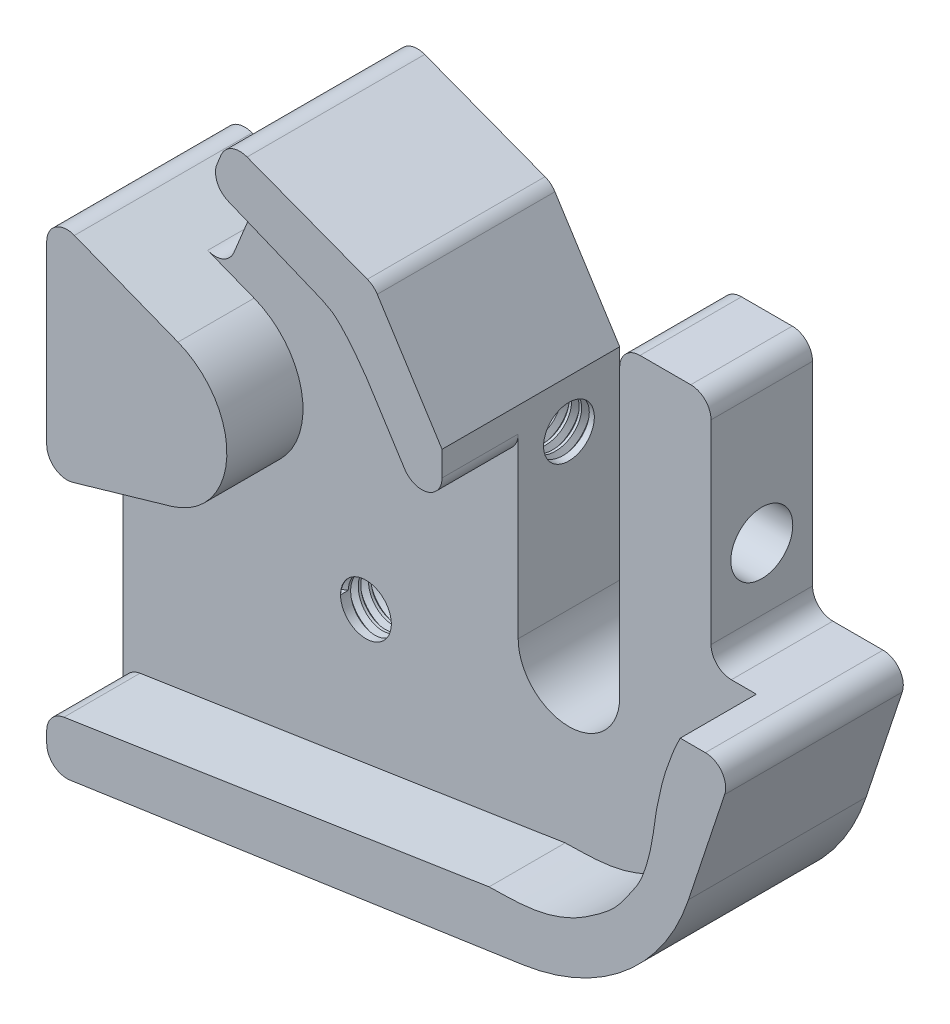
SolidWorks part; units mm, degrees
ref_plane "Front Plane" through (0, 0, 0) normal (0, 0, 1) x (1, 0, 0)
ref_plane "Top Plane" through (0, 0, 0) normal (0, 1, 0) x (1, 0, 0)
ref_plane "Right Plane" through (0, 0, 0) normal (1, 0, 0) x (0, 0, -1)
sketch "Sketch1" plane through (0, 0, 0) normal (0, 0, 1) x (1, 0, 0)
  line L0 (169.0465, 531.5792) -> (1384.9618, 942.3347) construction
  line L1 (17.1755, 0.269) -> (145.8355, -18.3486) construction
  line L2 (78.9683, 43.5936) -> (88.9683, 43.5936)
  line L3 (88.9683, 43.5936) -> (88.9683, 26.5936)
  line L4 (88.9683, 26.5936) -> (78.9683, 26.5936)
  line L5 (78.9683, 26.5936) -> (78.9683, 43.5936)
  line L6 (77.9414, 43.8024) -> (71.5407, 53.8656)
  line L7 (56.0381, 62.9033) -> (67.1668, 58.333)
  line L8 (88.9683, 43.5936) -> (88.9683, 61.7655)
  line L9 (88.9683, 61.7655) -> (97.9683, 61.7655)
  line L10 (77.9414, 43.8024) -> (78.9683, 42.1878)
  line L11 (20.6229, 24.1202) -> (53.1029, 33.5417)
  line L12 (23.9133, 59.0209) -> (55.1963, 46.7648)
  line L13 (56.0381, 62.9033) -> (50.2123, 48.7174)
  line L14 (70.5008, 62.7543) -> (72.231, 62.0968)
  line L15 (20.6228, 1.7639) -> (20.6229, 24.1202)
  line L16 (20.6229, 24.1202) -> (20.6229, 30.1202)
  line L17 (103.2745, 61.7655) -> (97.9683, 61.7655)
  line L18 (20.6229, 30.1202) -> (43.6301, 36.7939)
  line L19 (23.9133, 59.0209) -> (22.0894, 54.3655)
  line L20 (22.0894, 54.3655) -> (44.4958, 45.587)
  line L21 (78.9683, 43.5936) -> (78.9683, 49.4415)
  line L22 (57.9376, 67.5285) -> (70.5008, 62.7543)
  line L23 (83.9683, 38.5936) -> (107.6777, 38.5936)
  line L24 (40.0198, 35.7467) -> (40.0198, 47.3406)
  line L25 (40.0198, 47.3406) -> (40.0198, 52.7107)
  line L26 (56.0381, 62.9033) -> (57.9376, 67.5285)
  line L27 (103.4635, 40.5809) -> (108.336, 40.5809) construction
  line L28 (40.0198, 35.7467) -> (40.0198, 4.6135)
  line L29 (108.336, 40.5809) -> (99.307, 13.3233)
  line L30 (97.9683, 61.7655) -> (97.9683, 40.5809)
  line L31 (99.307, 13.3233) -> (20.6228, 1.7639)
  line L32 (83.9683, 43.5936) -> (83.9683, 46.6936)
  line L33 (20.6228, 6.4639) -> (20.6228, 6.7639)
  line L34 (20.6228, 6.7639) -> (83.6, 16.4882)
  line L35 (20.6229, 30.1202) -> (20.6229, 61.7655)
  line L36 (23.9133, 59.0209) -> (20.6229, 60.3101)
  line L37 (22.0894, 54.3655) -> (20.6229, 54.94)
  line L38 (73.7743, 50.3539) -> (77.9932, 53.0374) construction
  line L39 (77.9932, 53.0374) -> (71.1704, 63.7644)
  line L40 (77.9932, 53.0374) -> (78.9683, 51.5043)
  line L41 (78.9683, 51.5043) -> (78.9683, 49.4415)
  line L42 (97.9683, 40.5809) -> (97.9683, 38.5936)
  line L47 (97.9683, 40.5809) -> (103.4635, 40.5809) construction
  circle A0 centre (83.9683, 31.5936) radius 5
  circle A1 centre (83.9683, 38.5936) radius 5
  circle A5 centre (50.1903, 40.5872) radius 7.578
  circle A6 centre (103.2745, 54.3655) radius 4.4
  circle A7 centre (103.2745, 54.3655) radius 7.4
  circle A8 centre (83.9683, 31.5936) radius 20.3057
  spline S0 degree 3 poles (67.1668, 58.333) (67.5307, 58.1482) (68.2163, 57.8297) (69.7375, 56.3376) (70.7671, 54.998) (71.5407, 53.8656) knots 0 0 0 0 0.194176 0.353383 1 1 1 1
  spline S1 degree 3 poles (83.6, 16.4882) (85.4172, 16.5376) (87.878, 16.5192) (90.6726, 17.4205) (92.3949, 18.1773) (94.0998, 19.3373) (95.7619, 20.5842) (96.8381, 21.8934) (97.5722, 23.0215) (98.2993, 24.0127) (98.8168, 25.1807) (99.3382, 26.7948) (99.7545, 28.7331) (99.9792, 30.8782) (100.4112, 32.873) (100.8434, 34.6928) (101.4168, 36.2088) (101.8572, 37.4461) (102.3579, 38.4137) (102.8415, 39.4999) (103.165, 40.2018) (103.4635, 40.5809) knots 0 0 0 0 0.157684 0.206761 0.251698 0.319001 0.383658 0.429514 0.463788 0.499543 0.534878 0.573031 0.645405 0.704849 0.75836 0.820852 0.865423 0.897677 0.933689 0.958942 1 1 1 1
  spline S2 degree 3 poles (103.4635, 40.5809) (103.5281, 40.7021) (103.6539, 40.9177) (103.7777, 41.1891) (104.0324, 41.5752) (104.2845, 42.0418) (104.6133, 42.6639) (105.0506, 43.3284) (105.5376, 44.1633) (106.1189, 44.9679) (106.7473, 45.8247) (107.3304, 46.576) (107.8594, 47.2965) (108.3783, 47.8664) (108.8492, 48.4246) (109.2415, 48.9281) (109.5877, 49.4941) (110.1609, 50.7988) (110.3782, 52.0409) (110.5419, 52.9707) knots 0 0 0 0 0.032133 0.040138 0.080049 0.114202 0.15475 0.224504 0.279876 0.355143 0.430433 0.500504 0.552615 0.615873 0.660356 0.704255 0.748281 0.797656 1 1 1 1
  dimension "D7" = 5
  dimension "D5" = 8.8
  dimension "D6" = 14.8
  dimension "D1" = 130
  dimension "D2" = 10
  dimension "D3" = 17
  dimension "D4" = 9
  dimension "D8" = 5
  dimension "D9" = 5
  dimension "D10" = 5
extrude "Boss-Extrude1" add sketch "Sketch1" along normal blind 10 contours L34 S1 A8 L47 L30 L8 L3 L4 L5 L10 L6 | S0 L7 L13 L12 A5 L11 L28 L34 A8 L6 | A0 L5 L4 | A0 L4 L3 | A8 L30 A7 L9 L8 | L30 A7 | L30 A8 L8 L3 L23 L42 region at (78.4481, 40.3907, 0) region at (93.1258, 44.0387, 0) region at (93.2497, 55.6128, 0) region at (87.8514, 27.7104, 0) region at (80.0851, 27.7104, 0) region at (56.6282, 32.8832, 0) region at (97.1197, 54.3655, 0)
extrude "Boss-Extrude2" add sketch "Sketch1<3>" along normal blind 17.5 contours L7 S0 L6 A8 L41 L40 L39 L14 L22 L26 | L41 A8 L6 L10 L5 L21 | A5 | A5 L12 L25 L20 | A5 L20 L24 L18 | A5 L18 L28 L11 | A8 L34 L28 L31 | S1 L34 A8 | S1 A8 L29 L27 region at (77.4058, 47.7092, 0) region at (68.0812, 59.4299, 0) region at (102.7306, 38.1752, 0) region at (58.9314, 9.8932, 0) region at (105.1657, 35.2144, 0) region at (43.4702, 33.1986, 0) region at (43.8977, 48.9301, 0) region at (50.1903, 40.5872, 0) region at (41.5617, 41.668, 0)
sketch "Sketch1<3>" plane through (0, 0, 0) normal (0, 0, 1) x (1, 0, 0) same geometry as "Sketch1"
sketch "Sketch4" plane through (88.9683, 0, 0) normal (-1, 0, 0) x (0, 0, 1)
  line L0 (5, 61.7655) -> (5, 46.7655)
  line L2 (10, 61.7655) -> (0, 61.7655) construction
  circle A0 centre (5, 46.7655) radius 3.05
  dimension "D1" = 15
extrude "Cut-Extrude2" cut sketch "Sketch4" against normal blind 30 contours A0 region at (88.9683, 44.6698, 2.9043)
hole_wizard "Tap Drill for M6x1.0 Tap3" positions "3DSketch7" profile "Sketch10" hole size "M6x1.0" standard "ANSI Metric"
sketch3d "3DSketch7"
  line L0 (97.9683, 46.7655, 5) -> (88.9683, 46.7655, 5) construction
  point P0 (88.9683, 46.7655, 5)
sketch "Sketch10" plane through (88.9683, 46.7655, 5) normal (0, 1, 0) x (0, 0, -1)
  line L0 (0, 0) -> (0, 31.5022)
  line L1 (0, 31.5022) -> (2.5, 30)
  line L2 (2.5, 30) -> (2.5, 0)
  line L5 (2.5, 0) -> (0, 0)
  line L10 (0, 31.5022) -> (-2.5, 30) construction
  line L11 (0, -6.35) -> (0, 107.95) construction
  dimension "Hole Dia." = 5
  dimension "Hole Depth" = 30
  dimension "Drill Angle" = 118
thread "Thread2" pitch 1 method cut profile "Thread Profile2" start angle 0, offset 0, length 20, pitch 1, diameter 5
ref_plane "Plane2" through (78.9683, 46.7655, 7.5) normal (0, -1, 0) x (0, 0, 1)
sketch "Thread Profile2" plane through (78.9683, 46.7655, 7.5) normal (0, -1, 0) x (0, 0, 1)
  line L0 (0, 0) -> (0, 1) construction
  line L1 (0, 0) -> (0.5413, 0.3125)
  line L2 (0.5413, 0.3125) -> (0.5413, 0.4375)
  line L3 (0.5413, 0.4375) -> (0, 0.75)
  line L4 (0.5413, 0.375) -> (0, 0.375) construction
  line L11 (0, 0) -> (0, 0.75)
  point P2 (0, 0)
  dimension "Pitch" = 1
  dimension "Profile_Angle" = 60
  dimension "Profile_Land" = 0.125
  dimension "Profile_Height" = 0.5413
sketch "Sketch14" plane through (0, 0, 10) normal (0, 0, 1) x (1, 0, 0)
  line L0 (83.9683, 26.5936) -> (63.9683, 26.5936)
  arc A0 (78.9683, 31.5936) -> (88.9683, 31.5936) centre (83.9683, 31.5936) ccw construction
hole_wizard "Tap Drill for M6x1.0 Tap4" positions "3DSketch11" profile "Sketch15" hole size "M6x1.0" standard "ANSI Metric"
sketch3d "3DSketch11"
  point P0 (63.9683, 26.5936, 10)
sketch "Sketch15" plane through (63.9683, 26.5936, 10) normal (1, 0, 0) x (0, -1, 0)
  line L0 (0, 0) -> (0, 31.5022)
  line L1 (0, 31.5022) -> (2.5, 30)
  line L2 (2.5, 30) -> (2.5, 0)
  line L5 (2.5, 0) -> (0, 0)
  line L10 (0, 31.5022) -> (-2.5, 30) construction
  line L11 (0, -6.35) -> (0, 107.95) construction
  dimension "Hole Dia." = 5
  dimension "Hole Depth" = 30
  dimension "Drill Angle" = 118
thread "Thread3" pitch 1 method cut profile "Thread Profile3" start angle 0, offset 0, length 20, pitch 1, diameter 5
ref_plane "Plane3" through (61.4683, 26.5936, 10) normal (0, -1, 0) x (-1, 0, 0)
sketch "Thread Profile3" plane through (61.4683, 26.5936, 10) normal (0, -1, 0) x (-1, 0, 0)
  line L0 (0, 0) -> (0, 1) construction
  line L1 (0, 0) -> (0.5413, 0.3125)
  line L2 (0.5413, 0.3125) -> (0.5413, 0.4375)
  line L3 (0.5413, 0.4375) -> (0, 0.75)
  line L4 (0.5413, 0.375) -> (0, 0.375) construction
  line L11 (0, 0) -> (0, 0.75)
  point P2 (0, 0)
  dimension "Pitch" = 1
  dimension "Profile_Angle" = 60
  dimension "Profile_Land" = 0.125
  dimension "Profile_Height" = 0.5413
fillet "Fillet1" radius 2 13 edges at (97.9683, 61.7655, 5) (88.9683, 61.7655, 5) (57.9376, 67.5285, 8.75) (56.0381, 62.9033, 13.75) (78.9683, 42.1878, 13.75) (50.2123, 48.7174, 5) (40.0198, 4.6135, 8.75) (40.0198, 9.759, 13.75) (40.0198, 29.7467, 13.75) (40.0198, 52.7107, 8.75) (72.231, 62.0968, 8.75) (107.6777, 38.5936, 8.75) (97.9683, 38.5936, 5)
